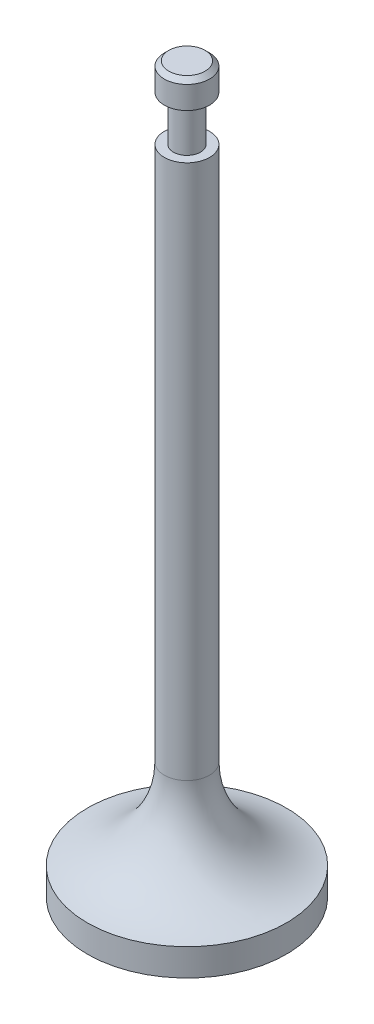
SolidWorks part; units mm, degrees
ref_plane "Front Plane" through (0, 0, 0) normal (0, 0, 1) x (1, 0, 0)
ref_plane "Top Plane" through (0, 0, 0) normal (0, 1, 0) x (1, 0, 0)
ref_plane "Right Plane" through (0, 0, 0) normal (1, 0, 0) x (0, 0, -1)
sketch "Sketch1" plane through (0, 0, 0) normal (1, 0, 0) x (0, 0, -1)
  line L0 (0, 0) -> (0, -80)
  line L1 (0, -80) -> (11, -80)
  line L2 (11, -80) -> (11, -77)
  line L3 (11, -77) -> (2.5, -77)
  line L4 (2.5, -77) -> (2.5, -8)
  line L5 (2.5, -8) -> (1.4957, -8)
  line L6 (1.4957, -8) -> (1.4957, -3)
  line L7 (1.4957, -3) -> (2.5, -3)
  line L8 (2.5, -3) -> (2.5, 0)
  line L9 (2.5, 0) -> (0, 0)
  point P4 (1.4957, -3)
  dimension "D1" = 80
  dimension "D2" = 11
  dimension "D3" = 3
  dimension "D4" = 2.5
  dimension "D5" = 3
  dimension "D6" = 5
  dimension "D7" = 2.5
  dimension "D8" = 1.0043
revolve "Revolve1" add sketch "Sketch1" angle 360 about L0
chamfer "Chamfer1" distance 0.5 angle 45 1 edges at (0, 0, 2.5)
fillet "Fillet1" radius 10 1 edges at (0, -77, 2.5)
